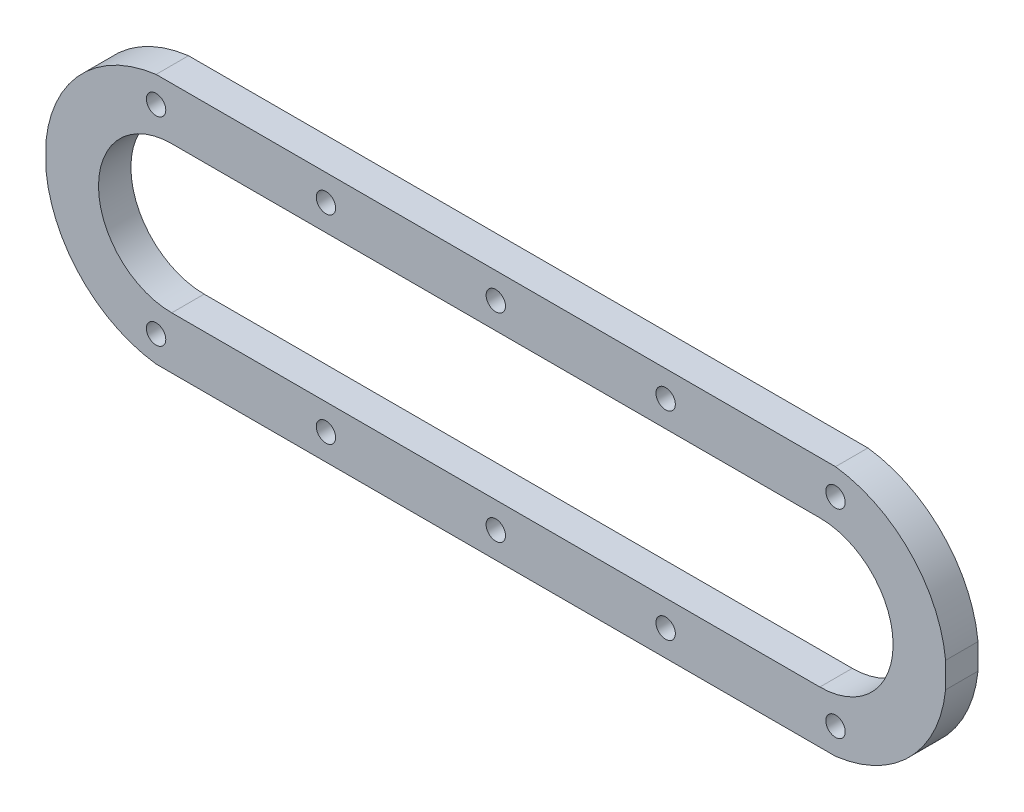
SolidWorks part; units mm, degrees
ref_plane "Front" through (0, 0, 0) normal (0, 0, 1) x (1, 0, 0)
ref_plane "Top" through (0, 0, 0) normal (0, 1, 0) x (1, 0, 0)
ref_plane "Right" through (0, 0, 0) normal (1, 0, 0) x (0, 0, -1)
sketch "Sketch1" plane through (0, 0, 0) normal (0, 0, 1) x (1, 0, 0)
  line L1 (88.138, 24.5745) -> (-88.138, 24.5745)
  line L2 (88.138, 24.5745) -> (88.138, -24.5745)
  line L3 (88.138, -24.5745) -> (-88.138, -24.5745)
  line L4 (-88.138, 24.5745) -> (-88.138, -24.5745)
  line L5 (88.138, 24.5745) -> (-88.138, -24.5745) construction
  line L6 (88.138, -24.5745) -> (-88.138, 24.5745) construction
  point P0 (0, 0)
  dimension "D1" = 176.276
  dimension "D2" = 49.149
extrude "Boss-Extrude1" add sketch "Sketch1" along normal blind 6.35
sketch "Sketch2" plane through (0, 0, 6.35) normal (0, 0, 1) x (1, 0, 0)
  line L0 (63.5, 0) -> (-63.5, 0) construction
  line L1 (63.5, -14.351) -> (-63.5, -14.351)
  line L2 (63.5, 14.351) -> (-63.5, 14.351)
  arc A0 (63.5, -14.351) -> (63.5, 14.351) centre (63.5, 0) ccw
  arc A1 (-63.5, 14.351) -> (-63.5, -14.351) centre (-63.5, 0) ccw
  point P2 (0, 0)
  dimension "D1" = 127
  dimension "D2" = 28.702
extrude "Cut-Extrude1" cut sketch "Sketch2" against normal through all
sketch "Sketch8" plane through (0, 0, 6.35) normal (0, 0, 1) x (1, 0, 0)
  line L4 (-63.5, 24.765) -> (63.5, 24.765)
  line L5 (-63.5, 14.351) -> (63.5, 14.351)
  line L6 (-63.5, -14.351) -> (63.5, -14.351)
  line L7 (-63.5, -24.765) -> (63.5, -24.765)
  arc A5 (-63.5, 14.351) -> (-63.5, -14.351) centre (-63.5, 0) ccw
  arc A6 (-63.5, 24.765) -> (-63.5, -24.765) centre (-63.5, 0) ccw
  arc A7 (63.5, 14.351) -> (63.5, -14.351) centre (63.5, 0) cw
  arc A8 (63.5, 24.765) -> (63.5, -24.765) centre (63.5, 0) cw
  line M5 (-88.138, 24.5745) -> (-88.138, -24.5745)
  line M6 (-88.138, -24.5745) -> (88.138, -24.5745)
  line M7 (88.138, -24.5745) -> (88.138, 24.5745)
  line M8 (88.138, 24.5745) -> (-88.138, 24.5745)
  dimension "D1" = 10.414
  dimension "D2" = 10.414
extrude "Cut-Extrude4" cut sketch "Sketch8" against normal through all contours A6 M8 M5 | A6 M5 M6 | A8 M8 M7 | A8 M7 M6 region at (-82.8086, 19.1871, 6.35) region at (82.8086, 19.1871, 6.35) region at (-82.8086, -19.1871, 6.35) region at (82.8086, -19.1871, 6.35)
sketch "Sketch12" plane through (0, 0, 6.35) normal (0, 0, 1) x (1, 0, 0)
  circle A0 centre (-33.2829, 19.4627) radius 2.5527
  circle A1 centre (-66.5658, 19.4627) radius 2.5527
  circle A2 centre (0, 19.4627) radius 2.5527
  circle A3 centre (66.5658, 19.4627) radius 2.5527
  circle A4 centre (33.2829, 19.4628) radius 2.5527
  circle A5 centre (0, -19.4627) radius 2.5527
  circle A6 centre (-33.2829, -19.4627) radius 2.5527
  circle A7 centre (-66.5658, -19.4627) radius 2.5527
  circle A8 centre (33.2829, -19.4627) radius 2.5527
  circle A9 centre (66.5658, -19.4627) radius 2.5527
  dimension "D1" = 5.1054
hole_wizard "#10-24 Tapped Hole1" positions "Sketch15" profile "Sketch16" tap size "#10-24" standard "ANSI Inch" end condition through all
sketch "Sketch15" plane through (0, 0, 6.35) normal (0, 0, 1) x (1, 0, 0)
  point P0 (-66.5658, 19.4627)
  point P3 (-33.2829, 19.4627)
  point P6 (0, 19.4627)
  point P9 (33.2829, 19.4628)
  point P12 (66.5658, 19.4627)
  point P15 (66.5658, -19.4627)
  point P18 (33.2829, -19.4627)
  point P21 (0, -19.4627)
  point P24 (-33.2829, -19.4627)
  point P27 (-66.5658, -19.4627)
sketch "Sketch16" plane through (-66.5658, 19.4627, 6.35) normal (1, 0, 0) x (0, -1, 0)
  line L0 (0, 0) -> (0, 6.35)
  line L1 (0, 6.35) -> (1.8986, 6.35)
  line L2 (1.8986, 6.35) -> (1.8986, 0)
  line L5 (1.8986, 0) -> (0, 0)
  line L11 (0, -6.35) -> (0, 107.95) construction
  dimension "Thread Major Dia." = 3.7973
  dimension "Thru Tap Drill Depth" = 6.35
